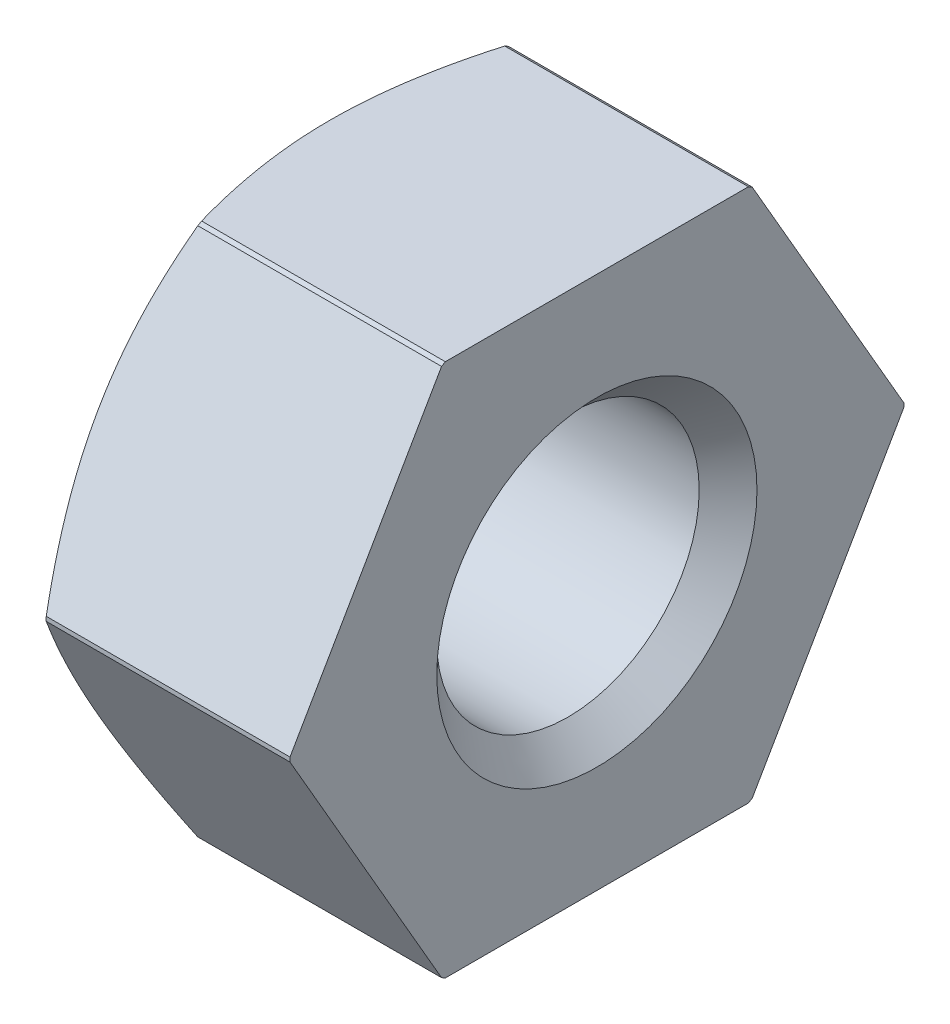
SolidWorks part; units mm, degrees
ref_plane "前视基准面" through (0, 0, 0) normal (0, 0, 1) x (1, 0, 0)
ref_plane "上视基准面" through (0, 0, 0) normal (0, 1, 0) x (1, 0, 0)
ref_plane "右视基准面" through (0, 0, 0) normal (1, 0, 0) x (0, 0, -1)
sketch "草图1" plane through (0, 0, 0) normal (0, 0, 1) x (1, 0, 0)
  line L0 (-2.5, 0) -> (-2.5, 5)
  line L1 (-2.5, 5) -> (-2.067, 5.75)
  line L2 (-2.067, 5.75) -> (2.5, 5.75)
  line L3 (2.5, 5.75) -> (2.5, 0)
  line L4 (2.5, 0) -> (-2.5, 0)
  line L5 (2.5, 0) -> (-2.5, 0) construction
revolve "旋转1" add sketch "草图1" angle 360 about L5 reverse direction yes
sketch "草图2" plane through (0, 0, 0) normal (0, 0, 1) x (1, 0, 0)
  line L0 (-2.5, 0) -> (-2.5, 3)
  line L1 (-2.5, 3) -> (-1.9585, 2.4585)
  line L2 (-1.9585, 2.4585) -> (1.9585, 2.4585)
  line L3 (1.9585, 2.4585) -> (2.5, 3)
  line L4 (2.5, 3) -> (2.5, 0)
  line L5 (2.5, 0) -> (-2.5, 0)
  line L6 (2.5, 0) -> (-2.5, 0) construction
revolve "切除-旋转1" cut sketch "草图2" angle 360 about L6 reverse direction yes
cosmetic thread "装饰螺纹线1" parameters "D1"=5, "D2"=6
sketch "草图3" plane through (0, 0, 0) normal (1, 0, 0) x (0, 0, -1)
  line L0 (-10, 10) -> (-10, -10)
  line L1 (-10, -10) -> (10, -10)
  line L2 (10, -10) -> (10, 10)
  line L3 (10, 10) -> (-10, 10)
  line L4 (-5.7735, 0) -> (-2.8868, -5)
  line L5 (-2.8868, -5) -> (2.8868, -5)
  line L6 (2.8868, -5) -> (5.7735, 0)
  line L7 (5.7735, 0) -> (2.8868, 5)
  line L8 (2.8868, 5) -> (-2.8868, 5)
  line L9 (-2.8868, 5) -> (-5.7735, 0)
extrude "切除-拉伸1" cut sketch "草图3" along normal blind 2.5 and the other way blind 2.5
ref_plane "C1 XY" through (0, 0, 0) normal (0, 0, 1) x (1, 0, 0)
ref_plane "C1 XZ" through (0, 0, 0) normal (0, -1, 0) x (-1, 0, 0)
ref_plane "C1 YZ" through (2.5, 0, 0) normal (1, 0, 0) x (0, 0, -1)
ref_axis "C1 X" through (-80.9, 0, 0) along (1, 0, 0)
ref_axis "C1 Y" through (2.5, -50, 0) along (0, 1, 0)
ref_axis "C1 Z" through (2.5, 0, 80.9) along (0, 0, -1)
sketch3d "C1"
  point P0 (2.5, 0, 0)
